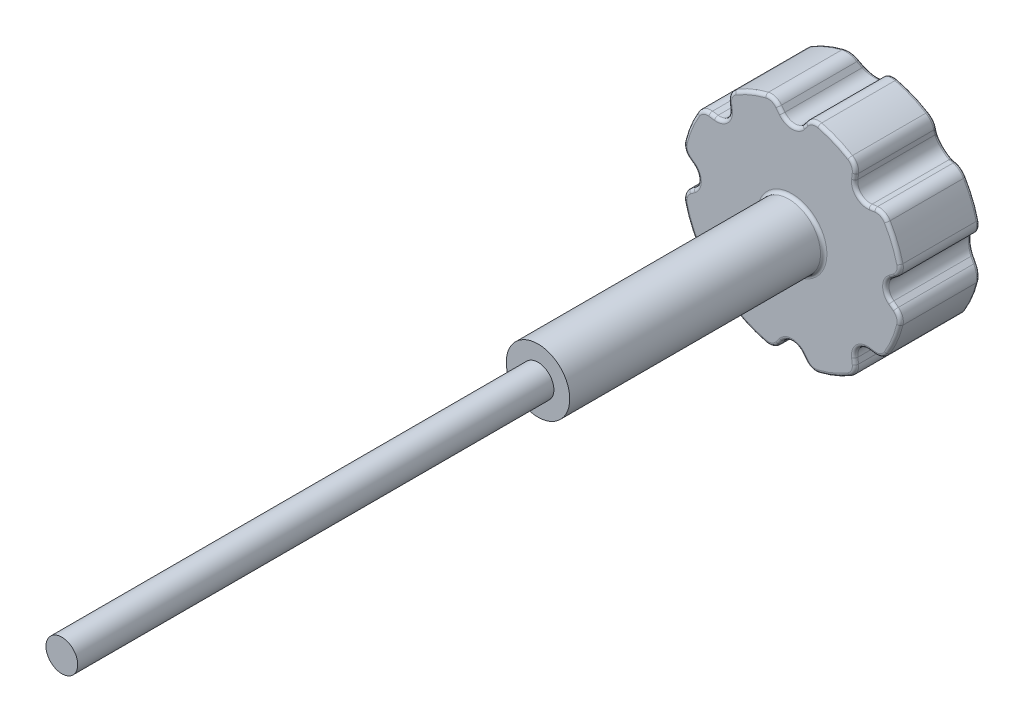
SolidWorks part; units mm, degrees
ref_plane "Front Plane" through (0, 0, 0) normal (0, 0, 1) x (1, 0, 0)
ref_plane "Top Plane" through (0, 0, 0) normal (0, 1, 0) x (1, 0, 0)
ref_plane "Right Plane" through (0, 0, 0) normal (1, 0, 0) x (0, 0, -1)
sketch "Sketch1" plane through (0, 0, 0) normal (0, 0, 1) x (1, 0, 0)
  circle A0 centre (0, 0) radius 1
  dimension "D1" = 2
extrude "Boss-Extrude1" add sketch "Sketch1" along normal blind 8
sketch "Sketch2" plane through (0, 0, 8) normal (0, 0, 1) x (1, 0, 0)
  circle A0 centre (0, 0) radius 0.5
  dimension "D1" = 1
extrude "Boss-Extrude2" add sketch "Sketch2" along normal blind 15
sketch "Sketch3" plane through (0, 0, 0) normal (0, 0, -1) x (-1, 0, 0)
  circle A0 centre (0, 0) radius 3.5
  dimension "D1" = 7
extrude "Boss-Extrude3" add sketch "Sketch3" along normal blind 2.75
chamfer "Chamfer1" distance 0.75 angle 20 1 edges at (-3.5, 0, -2.75) first distance on face at (-3.5, 0, -2.75)
sketch "Sketch4" plane through (0, 0, -2.75) normal (0, 0, -1) x (-1, 0, 0)
  line L0 (-1, 4) -> (0, 2.7)
  line L1 (0, 3.85) -> (0, -3.85) construction
  line L2 (0, 2.7) -> (1, 4)
  line L3 (1, 4) -> (-1, 4)
  line L4 (3.85, 0) -> (-3.85, 0) construction
  dimension "D1" = 2.7
  dimension "D2" = 4
  dimension "D3" = 1
  dimension "D4" = 1
extrude "Cut-Extrude1" cut sketch "Sketch4" against normal blind 2.75
pattern_circular "CirPattern1" count 8 over 360 about axis through (0, 0, -2.477) along (0, 0, 1) of "Cut-Extrude1"
fillet "Fillet1" radius 0.4 8 edges at (1.9092, -1.9092, -1.375) (0, -2.7, -1.375) (-1.9092, -1.9092, -1.375) (-2.7, 0, -1.375) (-1.9092, 1.9092, -1.375) (0, 2.7, -1.375) (2.7, 0, -1.375) (1.9092, 1.9092, -1.375)
fillet "Fillet2" radius 0.4 16 edges at (-3.4519, -0.5784, -1.2385) (-3.4519, 0.5784, -1.2385) (-2.0319, 2.8498, -1.2385) (-2.8498, 2.0319, -1.2385) (-0.5784, 3.4519, -1.2385) (0.5784, 3.4519, -1.2385) (2.0319, 2.8498, -1.2385) (2.8498, 2.0319, -1.2385) (3.4519, 0.5784, -1.2385) (2.8498, -2.0319, -1.2385) (3.4519, -0.5784, -1.2385) (2.0319, -2.8498, -1.2385) (0.5784, -3.4519, -1.2385) (-0.5784, -3.4519, -1.2385) (-2.0319, -2.8498, -1.2385) (-2.8498, -2.0319, -1.2385)
fillet "Fillet3" radius 0.1 98 edges at (-1, 0, 0) (-2.956, 0, 0) (-3.1829, 0.3714, 0) (-3.3872, 0.6108, 0) (-3.2336, 1.3394, 0) (-2.827, 1.9633, 0) (-2.5133, 1.988, 0) (-2.0902, 2.0902, 0) (-1.988, 2.5133, 0) (-1.9633, 2.827, 0) (-1.3394, 3.2336, 0) (-0.6108, 3.3872, 0) (-0.3714, 3.1829, 0) (0, 2.956, 0) (0.3714, 3.1829, 0) (0.6108, 3.3872, 0) (1.3394, 3.2336, 0) (1.9633, 2.827, 0) (1.988, 2.5133, 0) (2.0902, 2.0902, 0) (2.5133, 1.988, 0) (2.827, 1.9633, 0) (3.2336, 1.3394, 0) (3.3872, 0.6108, 0) (3.1829, 0.3714, 0) (2.956, 0, 0) (3.1829, -0.3714, 0) (3.3872, -0.6108, 0) (3.2336, -1.3394, 0) (2.827, -1.9633, 0) (2.5133, -1.988, 0) (2.0902, -2.0902, 0) (1.988, -2.5133, 0) (1.9633, -2.827, 0) (1.3394, -3.2336, 0) (0.6108, -3.3872, 0) (0.3714, -3.1829, 0) (0, -2.956, 0) (-0.3714, -3.1829, 0) (-0.6108, -3.3872, 0) (-1.3394, -3.2336, 0) (-1.9633, -2.827, 0) (-1.988, -2.5133, 0) (-2.0902, -2.0902, 0) (-2.5133, -1.988, 0) (-2.827, -1.9633, 0) (-3.2336, -1.3394, 0) (-3.3872, -0.6108, 0) (-3.1829, -0.3714, 0) (-2.8644, -1.9427, -2.4912) (-2.1149, -2.0675, -2.6744) (-1.974, -2.8025, -2.5032) (-1.3394, -3.2336, -2.477) (-0.6517, -3.3992, -2.4912) (-0.0335, -2.9575, -2.6744) (0.5858, -3.3776, -2.5032) (1.3394, -3.2336, -2.477) (1.9427, -2.8644, -2.4912) (2.0675, -2.1149, -2.6744) (2.8025, -1.974, -2.5032) (3.2336, -1.3394, -2.477) (3.3992, -0.6517, -2.4912) (2.9575, -0.0335, -2.6744) (3.3776, 0.5858, -2.5032) (3.2336, 1.3394, -2.477) (2.8644, 1.9427, -2.4912) (2.1149, 2.0675, -2.6744) (1.974, 2.8025, -2.5032) (1.3394, 3.2336, -2.477) (0.6517, 3.3992, -2.4912) (0.0335, 2.9575, -2.6744) (-0.5858, 3.3776, -2.5032) (-1.3394, 3.2336, -2.477) (-1.9427, 2.8644, -2.4912) (-2.0675, 2.1149, -2.6744) (-2.8025, 1.974, -2.5032) (-3.2336, 1.3394, -2.477) (-3.3992, 0.6517, -2.4912) (-2.9575, 0.0335, -2.6744) (-3.3776, -0.5858, -2.5032) (-3.2336, -1.3394, -2.477) (-2.75, 0, -2.75)
sketch "Sketch5" plane through (0, 0, -2.75) normal (0, 0, -1) x (-1, 0, 0)
  line L0 (0, 3.85) -> (0, -3.85) construction
  line L1 (-1.25, 1.1) -> (1.25, 1.1)
  line L2 (-1.25, 1.1) -> (-1.25, 0.4)
  line L3 (-1.25, 0.4) -> (-0.35, 0.4)
  line L4 (1.25, 1.1) -> (1.25, 0.4)
  line L6 (-0.35, 0.4) -> (-0.35, -1.5)
  line L7 (-0.35, -1.5) -> (0.35, -1.5)
  line L8 (0.35, 0.4) -> (0.35, -1.5)
  line L9 (3.85, 0) -> (-3.85, 0) construction
  line L10 (0.35, 0.4) -> (1.25, 0.4)
  dimension "D1" = 0.7
  dimension "D2" = 0.7
  dimension "D3" = 0.35
  dimension "D4" = 1.5
  dimension "D5" = 2.5
  dimension "D6" = 1.25
  dimension "D7" = 0.4
extrude "Boss-Extrude4" add sketch "Sketch5" along normal blind 0.25
fillet "Fillet4" radius 0.1 24 edges at (0.35, -0.55, -2.75) (0, -1.5, -2.75) (-0.35, -0.55, -2.75) (-0.8, 0.4, -2.75) (-1.25, 0.75, -2.75) (0, 1.1, -2.75) (1.25, 0.75, -2.75) (0.8, 0.4, -2.75) (0, 1.1, -3) (-1.25, 0.75, -3) (-0.8, 0.4, -3) (-0.35, -0.55, -3) (0, -1.5, -3) (0.35, -0.55, -3) (0.8, 0.4, -3) (1.25, 0.75, -3) (-1.25, 1.1, -2.875) (-1.25, 0.4, -2.875) (-0.35, 0.4, -2.875) (0.35, -1.5, -2.875) (-0.35, -1.5, -2.875) (0.35, 0.4, -2.875) (1.25, 0.4, -2.875) (1.25, 1.1, -2.875)
